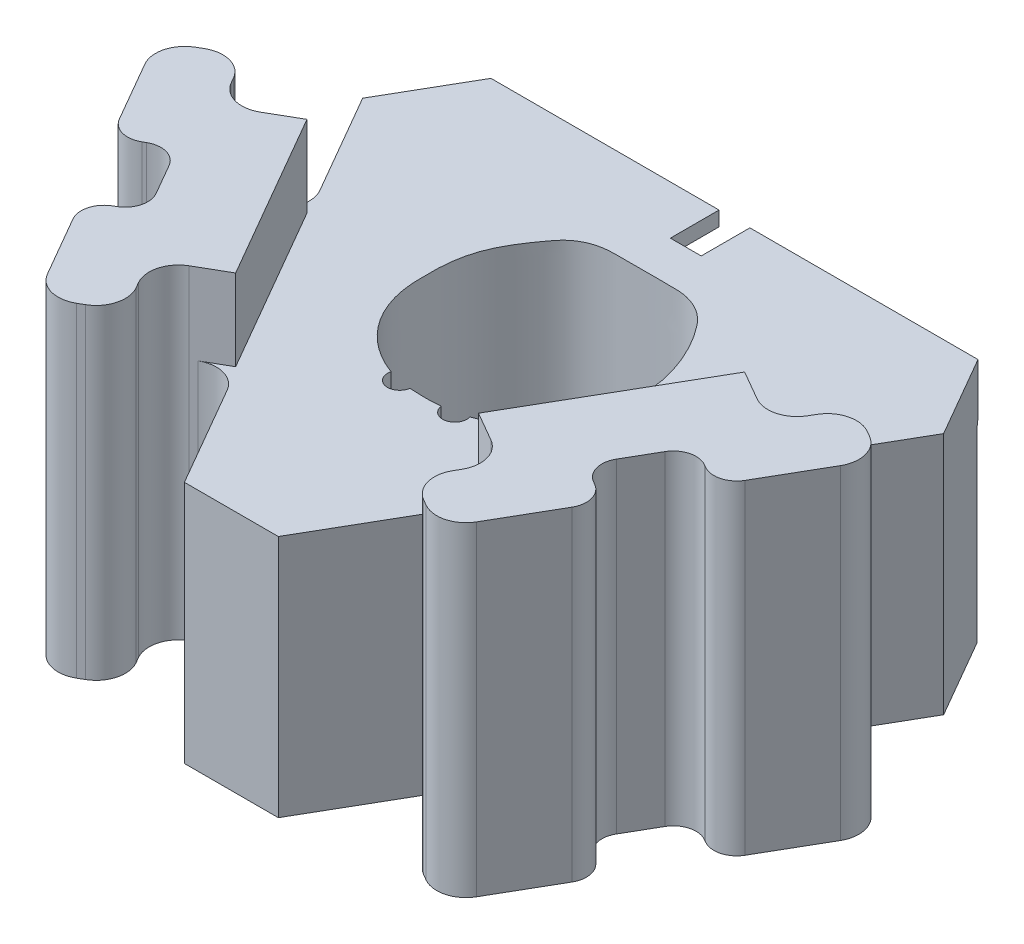
SolidWorks part; units mm, degrees
material "Nylon 101"
ref_plane "Plan de face" through (0, 0, 0) normal (0, 0, 1) x (1, 0, 0)
ref_plane "Plan de dessus" through (0, 0, 0) normal (0, 1, 0) x (1, 0, 0)
ref_plane "Plan de droite" through (0, 0, 0) normal (1, 0, 0) x (0, 0, -1)
sketch "Esquisse2" plane through (0, 0, 0) normal (0, 1, 0) x (1, 0, 0)
  line L5 (0, 0) -> (0, 12) construction
  line L6 (15, 12) -> (-15, 12)
  line L10 (2.8923, -18.9904) -> (17.8923, 6.9904)
  line L11 (0, 0) -> (10.3923, -6) construction
  line L12 (-17.8923, 6.9904) -> (-2.8923, -18.9904)
  line L13 (0, 0) -> (-10.3923, -6) construction
  line L14 (-15, 12) -> (-17.8923, 6.9904)
  line L15 (-2.8923, -18.9904) -> (2.8923, -18.9904)
  line L16 (17.8923, 6.9904) -> (15, 12)
  circle A0 centre (0, 0) radius 6.4543 construction
  spline S0 degree 3 poles (-6.4916, -0.6583) (-6.5698, 2.1101) (-5.6306, 3.6458) (-3.9015, 5.9899) (-2.756, 6.4428) (-0.8765, 6.4556) (1.1323, 6.4563) (2.7646, 6.4372) (3.9155, 5.9368) (5.686, 3.7258) (6.557, 1.3673) (6.4965, -0.4633) (6.5146, -1.1319) (6.2478, -3.8936) (4.3275, -6.6394) (0.5445, -7.077) (-0.4227, -7.0644) (-3.089, -6.9353) (-6.1206, -4.861) (-6.5148, -1.2298) (-6.4916, -0.6583) (-6.5698, 2.1101) (-5.6306, 3.6458) knots -0.028087 -0.008777 -0.000975 0 0.112372 0.130276 0.173621 0.187169 0.252205 0.26694 0.319781 0.34342 0.479691 0.498677 0.514296 0.542967 0.756721 0.785787 0.80456 0.825241 0.971913 0.991223 0.999025 1 1.112372 1.130276 1.173621 only from (-6.4978, -0.4355) to (-6.4978, -0.4355)
  point P6 (0, 12)
  point P15 (0, 0)
  dimension "D1" = 30
  dimension "D2" = 3
  dimension "D3" = 12
extrude "Boss.-Extru.1" add sketch "Esquisse2" along normal blind 15
sketch "Esquisse3" plane through (0, 0, 0) normal (0, 1, 0) x (1, 0, 0)
  line L0 (0, 0) -> (3.3, 0) construction
  line L1 (0, 0) -> (0, 3.3) construction
  line L2 (-16.4462, 9.4952) -> (0, 0) construction
  line L5 (-17.8923, 6.9904) -> (-15, 12) construction
  line L6 (0, 0) -> (16.4462, 9.4952) construction
  line L7 (15, 12) -> (17.8923, 6.9904) construction
  line L8 (0, 0) -> (0, -18.9904) construction
  line L9 (2.8923, -18.9904) -> (-2.8923, -18.9904) construction
  circle A0 centre (0, 0) radius 3.3 construction
  circle A5 centre (-12.9821, 7.4952) radius 2
  circle A7 centre (12.9821, 7.4952) radius 2
  circle A8 centre (0, -14.9904) radius 2
  point P23 (0, 0)
  dimension "D1" = 6.6
  dimension "D3" = 4
  dimension "D2" = 4
  dimension "D4" = 3
extrude "Enlèv. mat.-Extru.3" [suppressed] cut sketch "Esquisse3" against normal blind 8 and the other way through all from surface starting at face at (0, 15, 0)
sketch "Esquisse4" plane through (0, 0, 0) normal (0, 0, 1) x (1, 0, 0)
  line L0 (0, 0) -> (0, 7) construction
  line L1 (11, 3) -> (-11, 3) construction
  line L2 (11, 3) -> (11, 11) construction
  line L3 (11, 11) -> (-11, 11) construction
  line L4 (-11, 3) -> (-11, 11) construction
  line L5 (11, 3) -> (-11, 11) construction
  line L6 (11, 11) -> (-11, 3) construction
  line L8 (-17.8923, 0) -> (-2.8923, 0) construction
  circle A0 centre (-11, 11) radius 1.5
  circle A1 centre (11, 11) radius 1.5
  circle A2 centre (11, 3) radius 1.5
  circle A3 centre (-11, 3) radius 1.5
  point P0 (0, 7)
  dimension "D4" = 3
  dimension "D1" = 8
  dimension "D2" = 22
  dimension "D3" = 3
extrude "Enlèv. mat.-Extru.4" cut sketch "Esquisse4" along normal blind 8 from surface starting at face at (0, 7.5, -12)
sketch "Esquisse5" plane through (0, 0, 0) normal (0, 1, 0) x (1, 0, 0)
  line L0 (0, 0) -> (0, -18.9904) construction
  line L1 (2.8923, -18.9904) -> (-2.8923, -18.9904) construction
  line L2 (10.3923, -6) -> (17.3205, -10) construction
  line L3 (17.8923, 6.9904) -> (2.8923, -18.9904) construction
  line L4 (13.2205, -17.1014) -> (15.3705, -13.3775)
  line L5 (20.7617, -0.4397) -> (20.4153, -0.2397)
  line L6 (17.9564, -0.8986) -> (17.7564, -1.245)
  line L7 (15.2976, -1.9038) -> (13.3923, -0.8038)
  line L8 (13.3923, -0.8038) -> (7.3923, -11.1962)
  line L9 (9.2976, -12.2962) -> (7.3923, -11.1962)
  line L10 (9.7564, -15.1014) -> (9.9564, -14.755)
  line L11 (10.7617, -17.7603) -> (10.4153, -17.5603)
  line L12 (20.7617, -0.4397) -> (20.4153, -0.2397)
  line L13 (17.9564, -0.8986) -> (17.7564, -1.245)
  line L14 (15.2976, -1.9038) -> (13.3923, -0.8038)
  line L15 (9.2976, -12.2962) -> (7.3923, -11.1962)
  line L16 (9.7564, -15.1014) -> (9.9564, -14.755)
  line L17 (10.7617, -17.7603) -> (10.4153, -17.5603)
  line L18 (-17.3205, -10) -> (-18.5705, -7.8349) construction
  line L19 (-16.0705, -12.1651) -> (-17.3205, -10) construction
  line L20 (-10.3923, -6) -> (-17.3205, -10) construction
  line L21 (-19.2705, -6.6225) -> (-21.4205, -2.8986)
  line L22 (-17.1849, -7.0349) -> (-17.3581, -7.1349)
  line L23 (-14.1724, -9.4526) -> (-15.2724, -7.5474)
  line L24 (-14.8581, -11.4651) -> (-14.6849, -11.3651)
  line L25 (-10.7617, -17.7603) -> (-10.4153, -17.5603)
  line L26 (-9.7564, -15.1014) -> (-9.9564, -14.755)
  line L27 (-9.2976, -12.2962) -> (-7.3923, -11.1962)
  line L28 (-15.2976, -1.9038) -> (-13.3923, -0.8038)
  line L29 (-17.9564, -0.8986) -> (-17.7564, -1.245)
  line L30 (-20.7617, -0.4397) -> (-20.4153, -0.2397)
  line L31 (-10.7617, -17.7603) -> (-10.4153, -17.5603)
  line L32 (-9.7564, -15.1014) -> (-9.9564, -14.755)
  line L33 (14.8581, -11.4651) -> (14.6849, -11.3651)
  line L34 (14.1724, -9.4526) -> (15.2724, -7.5474)
  line L35 (17.1849, -7.0349) -> (17.3581, -7.1349)
  line L36 (16.0705, -12.1651) -> (17.3205, -10) construction
  line L37 (19.2705, -6.6225) -> (21.4205, -2.8986)
  line L38 (17.3205, -10) -> (18.5705, -7.8349) construction
  line L39 (-9.2976, -12.2962) -> (-7.3923, -11.1962)
  line L40 (-13.3923, -0.8038) -> (-7.3923, -11.1962)
  line L41 (-15.2976, -1.9038) -> (-13.3923, -0.8038)
  line L42 (-17.9564, -0.8986) -> (-17.7564, -1.245)
  line L43 (-20.7617, -0.4397) -> (-20.4153, -0.2397)
  line L44 (-13.2205, -17.1014) -> (-15.3705, -13.3775)
  arc A0 (10.7617, -17.7603) -> (13.2205, -17.1014) centre (11.6617, -16.2014) ccw
  arc A1 (9.7564, -15.1014) -> (10.4153, -17.5603) centre (11.3153, -16.0014) ccw
  arc A2 (9.2976, -12.2962) -> (9.9564, -14.755) centre (8.3976, -13.855) cw
  arc A3 (21.4205, -2.8986) -> (20.7617, -0.4397) centre (19.8617, -1.9986) ccw
  arc A4 (17.7564, -1.245) -> (15.2976, -1.9038) centre (16.1976, -0.345) cw
  arc A5 (20.4153, -0.2397) -> (17.9564, -0.8986) centre (19.5153, -1.7986) ccw
  arc A6 (10.4153, -17.5603) -> (9.7564, -15.1014) centre (11.3153, -16.0014) cw
  arc A7 (9.9564, -14.755) -> (9.2976, -12.2962) centre (8.3976, -13.855) ccw
  arc A8 (13.2205, -17.1014) -> (10.7617, -17.7603) centre (11.6617, -16.2014) cw
  arc A9 (15.2976, -1.9038) -> (17.7564, -1.245) centre (16.1976, -0.345) ccw
  arc A10 (17.9564, -0.8986) -> (20.4153, -0.2397) centre (19.5153, -1.7986) cw
  arc A11 (20.7617, -0.4397) -> (21.4205, -2.8986) centre (19.8617, -1.9986) cw
  arc A24 (17.3581, -7.1349) -> (19.2705, -6.6225) centre (18.0581, -5.9225) ccw
  arc A25 (15.2724, -7.5474) -> (17.1849, -7.0349) centre (16.4849, -8.2474) cw
  arc A26 (14.6849, -11.3651) -> (14.1724, -9.4526) centre (15.3849, -10.1526) cw
  arc A27 (14.8581, -11.4651) -> (15.3705, -13.3775) centre (14.1581, -12.6775) cw
  arc A28 (-14.8581, -11.4651) -> (-15.3705, -13.3775) centre (-14.1581, -12.6775) ccw
  arc A29 (-14.6849, -11.3651) -> (-14.1724, -9.4526) centre (-15.3849, -10.1526) ccw
  arc A30 (-15.2724, -7.5474) -> (-17.1849, -7.0349) centre (-16.4849, -8.2474) ccw
  arc A31 (-17.3581, -7.1349) -> (-19.2705, -6.6225) centre (-18.0581, -5.9225) cw
  arc A32 (-20.7617, -0.4397) -> (-21.4205, -2.8986) centre (-19.8617, -1.9986) ccw
  arc A33 (-17.9564, -0.8986) -> (-20.4153, -0.2397) centre (-19.5153, -1.7986) ccw
  arc A34 (-15.2976, -1.9038) -> (-17.7564, -1.245) centre (-16.1976, -0.345) cw
  arc A35 (-13.2205, -17.1014) -> (-10.7617, -17.7603) centre (-11.6617, -16.2014) ccw
  arc A36 (-9.9564, -14.755) -> (-9.2976, -12.2962) centre (-8.3976, -13.855) cw
  arc A37 (-10.4153, -17.5603) -> (-9.7564, -15.1014) centre (-11.3153, -16.0014) ccw
  arc A38 (-20.4153, -0.2397) -> (-17.9564, -0.8986) centre (-19.5153, -1.7986) cw
  arc A39 (-17.7564, -1.245) -> (-15.2976, -1.9038) centre (-16.1976, -0.345) ccw
  arc A40 (-21.4205, -2.8986) -> (-20.7617, -0.4397) centre (-19.8617, -1.9986) cw
  arc A41 (-9.2976, -12.2962) -> (-9.9564, -14.755) centre (-8.3976, -13.855) ccw
  arc A42 (-9.7564, -15.1014) -> (-10.4153, -17.5603) centre (-11.3153, -16.0014) cw
  arc A43 (-10.7617, -17.7603) -> (-13.2205, -17.1014) centre (-11.6617, -16.2014) cw
  point P19 (12.3205, -18.6603)
  point P22 (8.8564, -16.6603)
  point P25 (10.8564, -13.1962)
  point P28 (22.3205, -1.3397)
  point P31 (16.8564, -2.8038)
  point P34 (18.8564, 0.6603)
  point P64 (14.7224, -8.5)
  point P72 (15.9724, -6.3349)
  point P75 (13.4724, -10.6651)
  point P88 (-13.4724, -10.6651)
  point P89 (-15.9724, -6.3349)
  point P90 (-18.8564, 0.6603)
  point P91 (-16.8564, -2.8038)
  point P92 (-22.3205, -1.3397)
  point P93 (-10.8564, -13.1962)
  point P94 (-8.8564, -16.6603)
  point P95 (-12.3205, -18.6603)
  dimension "D5" = 1.8
  dimension "D8" = 1.4
  dimension "D1" = 8
  dimension "D2" = 4
  dimension "D3" = 4
  dimension "D4" = 10
  dimension "D6" = 3
  dimension "D7" = 5
extrude "Boss.-Extru.2" add sketch "Esquisse5" against normal up to surface and the other way blind 5 from surface contours L5 A5 L6 A4 L7 L8 L9 A2 L10 A1 L11 A0 L4 A3 | L25 A37 L26 A36 L27 L40 L28 A34 L29 A33 L30 A32 L21 A31 L22 A30 L23 A29 L24 A28 L44 A35 region at (13.999, 0, 8.0823) region at (-13.999, 0, 8.0823) up to face at (0, 0, 0) starting at face at (0, 15, 0)
fillet "Congé5" radius 1.8 4 edges at (13.3923, 7.5, 0.8038) (7.3923, 7.5, 11.1962) (-7.3923, 7.5, 11.1962) (-13.3923, 7.5, 0.8038)
sketch "Esquisse6" plane through (0, 0, 0) normal (0, 1, 0) x (1, 0, 0)
  line L0 (-13.3923, -0.8038) -> (-7.3923, -11.1962)
  line L1 (-7.3923, -11.1962) -> (-7.4789, -11.2462)
  line L2 (-7.3923, -11.1962) -> (-9.2976, -12.2962) construction
  line L3 (-7.4789, -11.2462) -> (-13.4789, -0.8538)
  line L4 (-13.3923, -0.8038) -> (-15.2976, -1.9038) construction
  line L5 (-13.4789, -0.8538) -> (-13.3923, -0.8038)
  line L6 (7.3923, -11.1962) -> (13.3923, -0.8038)
  line L7 (13.3923, -0.8038) -> (13.4789, -0.8538)
  line L8 (14.9512, -1.7038) -> (13.3923, -0.8038) construction
  line L9 (13.4789, -0.8538) -> (7.4789, -11.2462)
  line L10 (7.3923, -11.1962) -> (9.2976, -12.2962) construction
  line L11 (7.4789, -11.2462) -> (7.3923, -11.1962)
  dimension "D1" = 0.1
  dimension "D2" = 0.1
extrude "Enlèv. mat.-Extru.5" cut sketch "Esquisse6" along normal up to surface (20 mm away) from surface up to face at (-14.8463, 20, 8.5715) starting at face at (0, 15, 4.1586)
sketch "Esquisse7" plane through (0, 0, -12) normal (0, 0, -1) x (-1, 0, 0)
  line L0 (15, 15) -> (15, 0) construction
  line L1 (-15, 0) -> (15, 0) construction
  line L2 (-15, 0) -> (-15, 14) construction
  line L3 (-15, 14) -> (-0.85, 14) construction
  line L4 (15, 0) -> (15, 14) construction
  line L5 (-15, 15) -> (15, 15) construction
  line L6 (0.85, 0) -> (-0.85, 0)
  line L7 (0.85, 14) -> (0.85, 15) construction
  line L8 (0.85, 15) -> (-0.85, 15) construction
  line L9 (-0.85, 14) -> (-0.85, 15) construction
  line L10 (-0.85, 0) -> (-0.85, 14) construction
  line L11 (0.85, 0) -> (0.85, 14) construction
  line L12 (-0.85, 14) -> (0.85, 14) construction
  line L13 (0.85, 14) -> (15, 14) construction
  line L14 (-15.1, -0.1) -> (-15.1, 14.1)
  line L15 (-15.1, 14.1) -> (-0.95, 14.1)
  line L16 (-0.95, 14.1) -> (-0.95, 15.1)
  line L17 (0.95, 15.1) -> (-0.95, 15.1)
  line L18 (0.95, 14.1) -> (0.95, 15.1)
  line L19 (0.95, 14.1) -> (15.1, 14.1)
  line L20 (15.1, -0.1) -> (15.1, 14.1)
  line L21 (-15.1, -0.1) -> (15.1, -0.1)
  circle A0 centre (11, 11) radius 1.5 construction
  circle M9 centre (-11, 3) radius 1.5
  circle M10 centre (11, 11) radius 1.5
  circle M11 centre (11, 3) radius 1.5
  circle M12 centre (-11, 11) radius 1.5
  line M13 (-15, 0) -> (15, 0)
  line M14 (15, 0) -> (15, 15)
  line M15 (15, 15) -> (-15, 15)
  line M16 (-15, 15) -> (-15, 0)
  dimension "D1" = 3
  dimension "D2" = 0.85
  dimension "D3" = 0.85
  dimension "D4" = 0.1
extrude "Enlèv. mat.-Extru.6" cut sketch "Esquisse7" against normal blind 3 contours L14 L21 L20 L19 L15 M14 M13 M16 | L19 L18 L16 L15 M15 M16 M13 M14 M10 M12 M11 M9 | L18 L17 L16 M15 region at (-7.925, -0.0334, -12) region at (0, 7.0859, -12) region at (0, 15.05, -12)
fillet "Congé6" radius 3 2 edges at (-15.1, 14.1, -10.4134) (15.1, 14.1, -10.4134)
sketch "Esquisse8" plane through (0, 15, 0) normal (0, 1, 0) x (1, 0, 0)
  line L0 (0, 0) -> (0, -2.8854) construction
  circle A0 centre (-1.7, -6.9242) radius 0.75
  circle A1 centre (1.7, -6.9242) radius 0.75
  spline S0 degree 3 poles (-5.6306, 3.6458) (-6.5698, 2.1101) (-6.4916, -0.6583) (-6.5148, -1.2298) (-6.1206, -4.861) (-3.089, -6.9353) (-0.4227, -7.0644) (0.5445, -7.077) (4.3275, -6.6394) (6.2478, -3.8936) (6.5146, -1.1319) (6.4965, -0.4633) (6.557, 1.3673) (5.686, 3.7258) (3.9155, 5.9368) (2.7646, 6.4372) (1.1323, 6.4563) (-0.8765, 6.4556) (-2.756, 6.4428) (-3.9015, 5.9899) (-5.6306, 3.6458) (-6.5698, 2.1101) (-6.4916, -0.6583) knots -0.173621 -0.130276 -0.112372 0 0.000975 0.008777 0.028087 0.174759 0.19544 0.214213 0.243279 0.457033 0.485704 0.501323 0.520309 0.65658 0.680219 0.73306 0.747795 0.812831 0.826379 0.869724 0.887628 1 1.000975 1.008777 1.028087 only from (-6.4978, -0.4355) to (-6.4978, -0.4355) construction
  dimension "D2" = 1.5
  dimension "D1" = 1.7
extrude "Enlèv. mat.-Extru.7" cut sketch "Esquisse8" against normal through all
